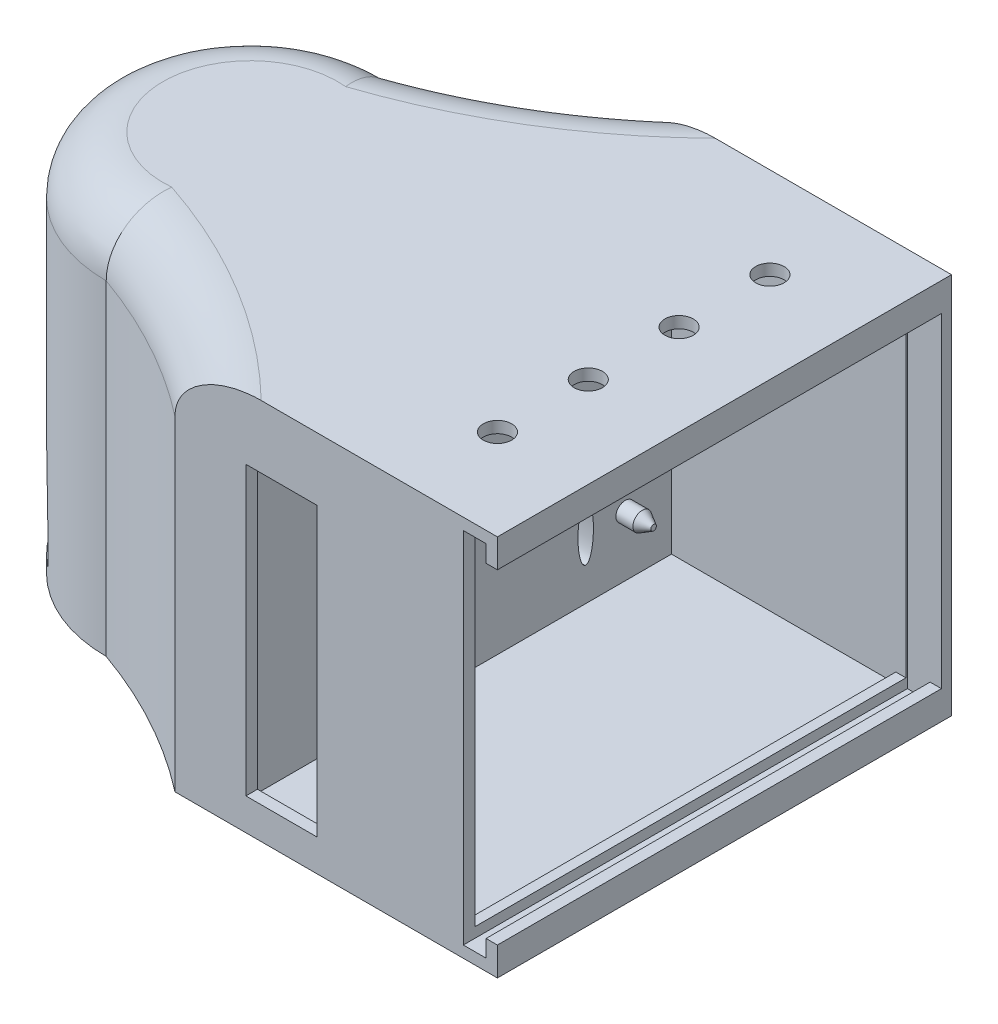
SolidWorks part; units mm, degrees
ref_plane "Front" through (0, 0, 0) normal (0, 0, 1) x (1, 0, 0)
ref_plane "Top" through (0, 0, 0) normal (0, 1, 0) x (1, 0, 0)
ref_plane "Right" through (0, 0, 0) normal (1, 0, 0) x (0, 0, -1)
sketch "Sketch1" plane through (0, 0, 0) normal (0, 1, 0) x (1, 0, 0)
  line L1 (-22.2874, 26.8069) -> (28.5126, 26.8069)
  line L2 (-22.2874, 26.8069) -> (-22.2874, -53.2031)
  line L3 (-22.2874, -53.2031) -> (28.5126, -53.2031)
  line L4 (28.5126, 26.8069) -> (28.5126, -53.2031)
  circle A0 centre (-49.0165, -13.1981) radius 25.4
  arc A1 (-49.0165, 12.2019) -> (-22.2874, 26.8069) centre (-80.7565, 102.0516) ccw
  arc A2 (-22.2874, -53.2031) -> (-49.0165, -38.5981) centre (-80.7565, -128.4478) ccw
  point P7 (-22.2874, -13.1981)
  dimension "D3" = 50.8
  dimension "D1" = 80.01
  dimension "D2" = 50.8
extrude "Boss-Extrude2" add sketch "Sketch1" along normal blind 67.31 contours A0 | A2 L2 A1 A0 | L4 L1 L2 L3 region at (3.1126, 0, 13.1981) region at (-23.131, 0, 13.1981) region at (-49.0165, 0, 13.1981)
fillet "Fillet1" radius 10 3 edges at (-35.0646, 67.31, 44.8257) (-74.4165, 67.31, 13.1981) (-35.0646, 67.31, -18.4296)
sketch "Sketch2" plane through (28.5126, 0, 0) normal (1, 0, 0) x (0, 0, -1)
  line L0 (26.8069, 67.31) -> (26.8069, 0) construction
  line L1 (-51.1711, 65.278) -> (24.7749, 65.278)
  line L2 (-51.1711, 65.278) -> (-51.1711, 2.032)
  line L3 (-51.1711, 2.032) -> (24.7749, 2.032)
  line L4 (24.7749, 65.278) -> (24.7749, 2.032)
  line L5 (26.8069, 0) -> (-53.2031, 0) construction
  line L6 (26.8069, 67.31) -> (-53.2031, 67.31) construction
  line L7 (-53.2031, 57.31) -> (-53.2031, 0) construction
  dimension "D1" = 2.032
  dimension "D2" = 2.032
  dimension "D3" = 2.032
  dimension "D4" = 2.032
extrude "Cut-Extrude1" cut sketch "Sketch2" against normal blind 41.31
sketch "Sketch3" plane through (-12.7974, 0, 0) normal (1, 0, 0) x (0, 0, -1)
  line L0 (-51.1711, 65.278) -> (-51.1711, 2.032) construction
  line L1 (-34.1711, 55.8247) -> (16.6289, 55.8247)
  line L2 (-34.1711, 55.8247) -> (-34.1711, 7.5647)
  line L3 (-34.1711, 7.5647) -> (16.6289, 7.5647)
  line L4 (16.6289, 55.8247) -> (16.6289, 7.5647)
  line L6 (-4.8692, 40.5847) -> (16.6289, 40.5847)
  line L7 (-4.8692, 40.5847) -> (-4.8692, 12.6447)
  line L8 (-4.8692, 12.6447) -> (16.6289, 12.6447)
  line L9 (16.6289, 40.5847) -> (16.6289, 12.6447)
  circle A0 centre (-34.1711, 55.8247) radius 1.651
  circle A1 centre (-34.1711, 7.5647) radius 1.651
  circle A2 centre (16.6289, 40.5847) radius 1.651
  circle A3 centre (16.6289, 12.6447) radius 1.651
  dimension "D4" = 3.302
  dimension "D1" = 50.8
  dimension "D2" = 48.26
  dimension "D3" = 17
  dimension "D5" = 27.94
  dimension "D6" = 15.24
extrude "Boss-Extrude3" add sketch "Sketch3" along normal blind 5 contours A0 | A2 | A3 | A1
chamfer "Chamfer1" distance 2 angle 30 4 edges at (-7.7974, 12.6447, -18.2799) (-7.7974, 40.5847, -18.2799) (-7.7974, 55.8247, 32.5201) (-7.7974, 7.5647, 32.5201) first distance on face at (-7.7974, 12.6447, -18.2799) first distance on face at (-7.7974, 40.5847, -18.2799) first distance on face at (-7.7974, 55.8247, 32.5201) first distance on face at (-7.7974, 7.5647, 32.5201)
ref_plane "Plane1" through (-76.2, 0, 0) normal (1, 0, 0) x (0, 0, -1)
sketch "Sketch4" plane through (-76.2, 0, 0) normal (1, 0, 0) x (0, 0, -1)
  line L0 (6.8907, 2.8887) -> (-33.2868, 2.8887)
  line L2 (-38.5981, 0) -> (12.2019, 0) construction
  ellipse E0 centre (-13.1981, 2.8887) end of major axis (-13.1981, 51.376) minor radius 20.0888 (-33.2868, 2.8887) -> (6.8907, 2.8887) cw
  point P6 (-13.1981, 0)
extrude "Cut-Extrude3" cut sketch "Sketch4" along normal blind 52
sketch "Sketch5" plane through (0, 0, 53.2031) normal (0, 0, 1) x (1, 0, 0)
  line L0 (-12.7974, 65.278) -> (-12.7974, 2.032) construction
  line L1 (-9.7974, 56.2313) -> (2.7256, 56.2313)
  line L2 (-9.7974, 56.2313) -> (-9.7974, 5.6244)
  line L3 (-9.7974, 5.6244) -> (2.7256, 5.6244)
  line L4 (2.7256, 56.2313) -> (2.7256, 5.6244)
  dimension "D1" = 3
ref_plane "Plane2" through (0, 0, 13.1981) normal (0, 0, 1) x (1, 0, 0)
sketch "Sketch7" plane through (0, 0, 13.1981) normal (0, 0, 1) x (1, 0, 0)
  line L1 (-44.9837, 19.6435) -> (-23.9837, 19.6435)
  line L2 (-44.9837, 19.6435) -> (-44.9837, 5.6435)
  line L3 (-44.9837, 5.6435) -> (-23.9837, 5.6435)
  line L4 (-23.9837, 19.6435) -> (-23.9837, 5.6435)
  dimension "D1" = 21
  dimension "D2" = 14
extrude "Cut-Extrude4" cut sketch "Sketch7" against normal blind 25 and the other way blind 25
sketch "Sketch8" plane through (-23.9837, 0, 0) normal (-1, 0, 0) x (0, 0, 1)
  ellipse E0 centre (-9.6654, 12.7751) end of major axis (-9.6654, 7.9051) minor radius 1.3674
  ellipse E1 centre (35.2422, 12.7751) end of major axis (35.2422, 7.9051) minor radius 1.3674
extrude "Cut-Extrude5" cut sketch "Sketch8" against normal through all
extrude "Cut-Extrude6" cut sketch "Sketch5" against normal blind 10
sketch "Sketch9" plane through (0, 67.31, 0) normal (0, 1, 0) x (1, 0, 0)
  line L0 (-7.1056, 26.8069) -> (28.5126, 26.8069) construction
  line L1 (28.5126, 26.8069) -> (28.5126, -53.2031) construction
  circle A0 centre (18.5126, -37.1931) radius 2.5
  circle A1 centre (18.5126, -21.1931) radius 2.5
  circle A2 centre (18.5126, -5.1931) radius 2.5
  circle A3 centre (18.5126, 10.8069) radius 2.5
  dimension "D1" = 5
  dimension "D2" = 16
  dimension "D3" = 16
  dimension "D4" = 16
  dimension "D5" = 16
  dimension "D6" = 10
extrude "Cut-Extrude7" cut sketch "Sketch9" against normal blind 10 contours A0 | A1 | A2 | A3
sketch "Sketch10" plane through (28.5126, 0, 0) normal (1, 0, 0) x (0, 0, -1)
  line L0 (24.7749, 65.278) -> (26.8069, 65.278)
  line L1 (26.8069, 67.31) -> (26.8069, 0) construction
  line L2 (-51.1711, 2.032) -> (-53.2031, 2.032)
  line L3 (26.8069, 65.278) -> (-53.2031, 65.278)
  line L4 (26.8069, 65.278) -> (26.8069, 67.31)
  line L5 (26.8069, 67.31) -> (-53.2031, 67.31)
  line L6 (-53.2031, 65.278) -> (-53.2031, 67.31)
  line L7 (-53.2031, 67.31) -> (-53.2031, 0) construction
  line L9 (-53.2031, 2.032) -> (26.8069, 2.032)
  line L10 (-53.2031, 2.032) -> (-53.2031, 0)
  line L11 (-53.2031, 0) -> (26.8069, 0)
  line L12 (26.8069, 2.032) -> (26.8069, 0)
extrude "Boss-Extrude4" add sketch "Sketch10" along normal blind 6 contours L3 L1 L0 L5 L6 L7 | L9 L12 L11 L10 region at (28.5126, 66.294, 13.1981)
sketch "Sketch11" plane through (0, 65.278, 0) normal (0, -1, 0) x (1, 0, 0)
  line L0 (34.5126, -26.8069) -> (28.5126, -26.8069) construction
  line L1 (34.5126, 53.2031) -> (32.5126, 53.2031)
  line L2 (34.5126, 53.2031) -> (34.5126, -26.8069)
  line L3 (34.5126, -26.8069) -> (32.5126, -26.8069)
  line L4 (32.5126, 53.2031) -> (32.5126, -26.8069)
  dimension "D1" = 2
extrude "Boss-Extrude6" add sketch "Sketch11" along normal blind 3
sketch "Sketch12" plane through (0, 2.032, 0) normal (0, 1, 0) x (1, 0, 0)
  line L0 (34.5126, -53.2031) -> (28.5126, -53.2031) construction
  line L1 (34.5126, 26.8069) -> (32.5126, 26.8069)
  line L2 (34.5126, 26.8069) -> (34.5126, -53.2031)
  line L3 (34.5126, -53.2031) -> (32.5126, -53.2031)
  line L4 (32.5126, 26.8069) -> (32.5126, -53.2031)
  dimension "D1" = 2
extrude "Boss-Extrude7" add sketch "Sketch12" along normal blind 3
sketch "Sketch13" plane through (0, 2.032, 0) normal (0, 1, 0) x (1, 0, 0)
  line L0 (-12.7974, -51.1711) -> (28.5126, -51.1711) construction
  line L1 (28.5126, 24.7749) -> (26.7346, 24.7749)
  line L2 (28.5126, 24.7749) -> (28.5126, -51.1711)
  line L3 (28.5126, -51.1711) -> (26.7346, -51.1711)
  line L4 (26.7346, 24.7749) -> (26.7346, -51.1711)
  dimension "D1" = 1.778
extrude "Boss-Extrude8" add sketch "Sketch13" along normal blind 1.778
sketch "Sketch14" plane through (0, 65.278, 0) normal (0, -1, 0) x (1, 0, 0)
  line L0 (-12.7974, -24.7749) -> (28.5126, -24.7749) construction
  line L1 (28.5126, 51.1711) -> (26.7346, 51.1711)
  line L2 (28.5126, 51.1711) -> (28.5126, -24.7749)
  line L3 (28.5126, -24.7749) -> (26.7346, -24.7749)
  line L4 (26.7346, 51.1711) -> (26.7346, -24.7749)
  point P7 (0, 0)
  dimension "D1" = 1.778
extrude "Boss-Extrude9" add sketch "Sketch14" along normal blind 1.778
sketch "Sketch15" plane through (0, 0, -26.8069) normal (0, 0, -1) x (-1, 0, 0)
  line L0 (-34.5126, 5.032) -> (-34.5126, 62.278)
  line L1 (-34.5126, 62.278) -> (-32.5126, 62.278)
  line L2 (-32.5126, 62.278) -> (-34.5126, 62.278) construction
  line L3 (-32.5126, 62.278) -> (-32.5126, 65.278) construction
  line L4 (-32.5126, 62.278) -> (-32.5126, 65.278)
  line L5 (-32.5126, 65.278) -> (-28.5126, 65.278)
  line L6 (-28.5126, 65.278) -> (-28.5126, 2.032) construction
  line L7 (-32.5126, 65.278) -> (-28.5126, 65.278) construction
  line L8 (-28.5126, 65.278) -> (-28.5126, 2.032)
  line L9 (-28.5126, 2.032) -> (-32.5126, 2.032)
  line L10 (-32.5126, 2.032) -> (-32.5126, 5.032)
  line L11 (-32.5126, 5.032) -> (-32.5126, 2.032) construction
  line L12 (-32.5126, 5.032) -> (-34.5126, 5.032)
extrude "Boss-Extrude10" add sketch "Sketch15" against normal blind 1.778
